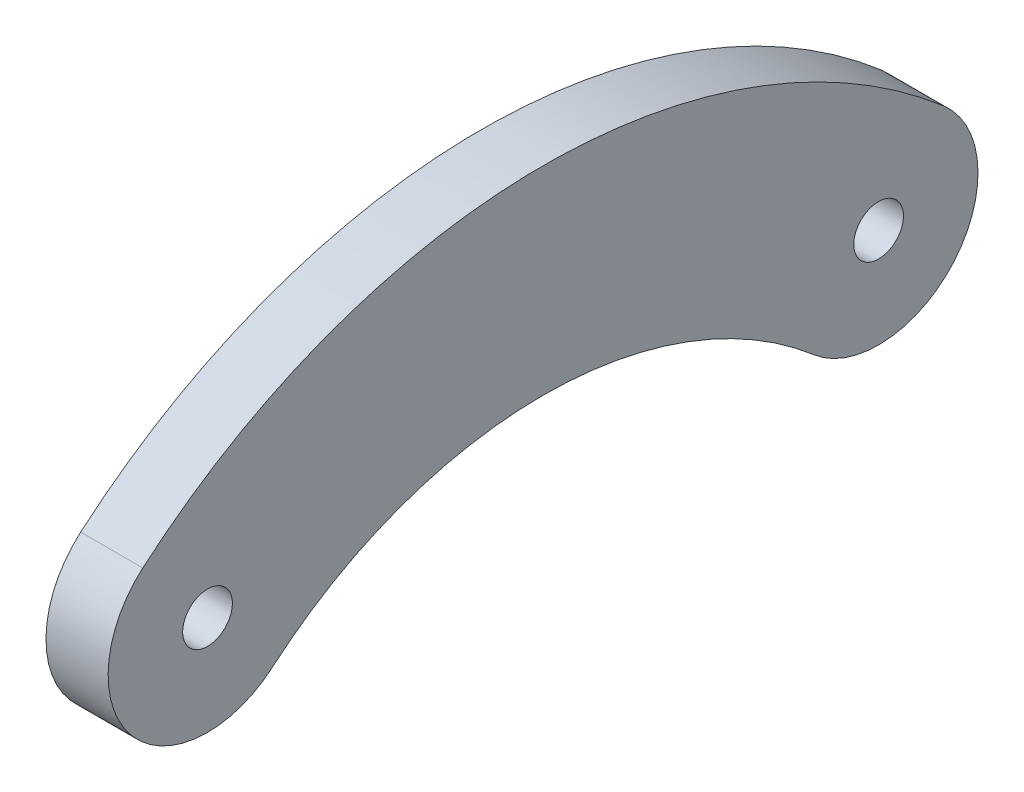
SolidWorks part; units mm, degrees
material "普通碳钢"
ref_plane "前视" through (0, 0, 0) normal (0, 0, 1) x (1, 0, 0)
ref_plane "上视" through (0, 0, 0) normal (0, 1, 0) x (1, 0, 0)
ref_plane "右视" through (0, 0, 0) normal (1, 0, 0) x (0, 0, -1)
sketch "草图1" plane through (0, 0, 0) normal (1, 0, 0) x (0, 0, -1)
  arc A0 (0, 0) -> (27, 0) centre (13.5, -15.725) cw construction
  arc A1 (29.6055, 3.035) -> (-2.6055, 3.035) centre (13.5, -15.725) ccw
  arc A2 (24.3945, -3.035) -> (2.6055, -3.035) centre (13.5, -15.725) ccw
  arc A3 (24.3945, -3.035) -> (29.6055, 3.035) centre (27, 0) ccw
  arc A4 (-2.6055, 3.035) -> (2.6055, -3.035) centre (0, 0) ccw
  circle A5 centre (0, 0) radius 1
  circle A6 centre (27, 0) radius 1
  point P3 (13.5, 5)
  dimension "D1" = 35
  dimension "D2" = 4
  dimension "D3" = 13
  dimension "D4" = 2
extrude "凸台-拉伸1" add sketch "草图1" along normal mid plane 2.5
